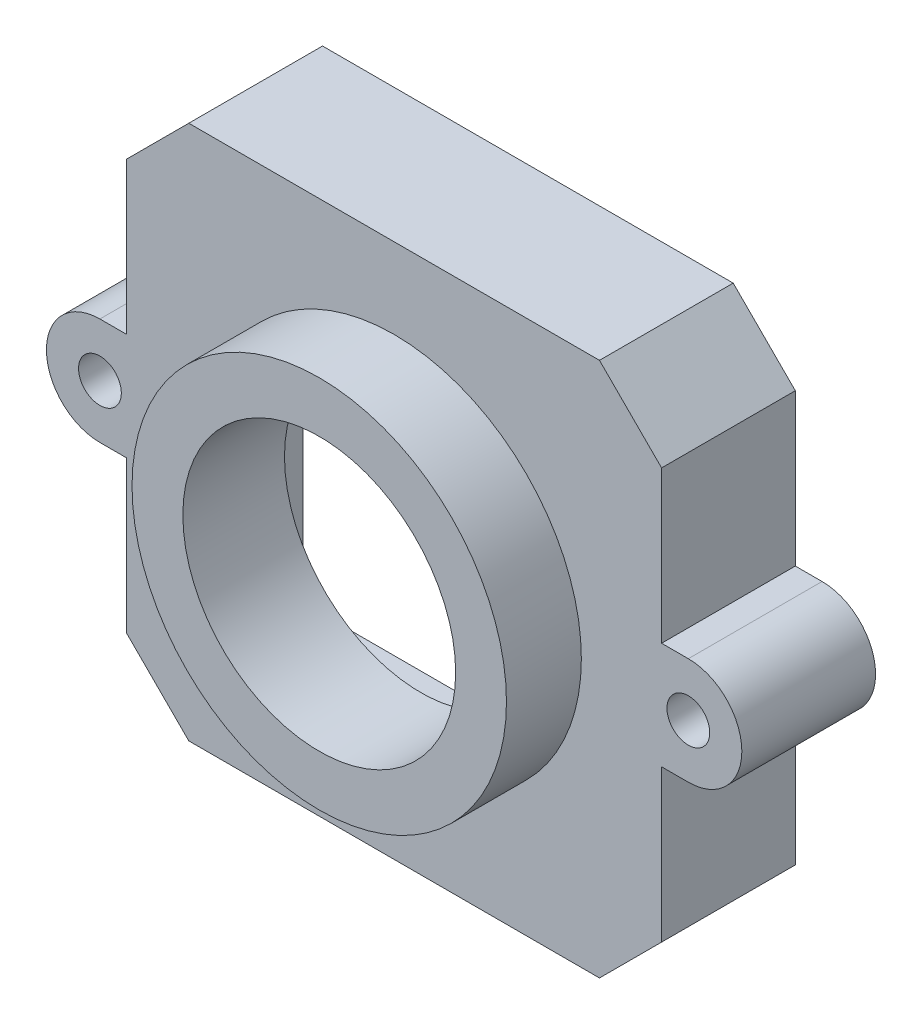
SolidWorks part; units mm, degrees
ref_plane "Front" through (0, 0, 0) normal (0, 0, 1) x (1, 0, 0)
ref_plane "Top" through (0, 0, 0) normal (0, 1, 0) x (1, 0, 0)
ref_plane "Right" through (0, 0, 0) normal (1, 0, 0) x (0, 0, -1)
sketch "Sketch1" plane through (0, 0, 0) normal (0, 0, 1) x (1, 0, 0)
  line L0 (-10, 7.6777) -> (-7.6777, 10)
  line L1 (-10, 10) -> (10, 10)
  line L2 (-10, 10) -> (-10, -10)
  line L3 (-10, -10) -> (10, -10)
  line L4 (10, 10) -> (10, -10)
  line L5 (7.6777, 10) -> (10, 7.6777)
  line L6 (-10, -7.6777) -> (-7.6777, -10)
  line L7 (7.6777, -10) -> (10, -7.6777)
  line L8 (10, 2) -> (11, 2)
  line L9 (10, -2) -> (11, -2)
  line L10 (-10, 2) -> (-11, 2)
  line L11 (-10, -2) -> (-11, -2)
  line L12 (-8.4, 7.0149) -> (-8.4, -7.0149)
  line L13 (-8.4, -7.0149) -> (-7.0149, -8.4)
  line L14 (-7.0149, -8.4) -> (7.0149, -8.4)
  line L15 (7.0149, -8.4) -> (8.4, -7.0149)
  line L16 (8.4, -7.0149) -> (8.4, 7.0149)
  line L17 (8.4, 7.0149) -> (7.0149, 8.4)
  line L18 (7.0149, 8.4) -> (-7.0149, 8.4)
  line L19 (-7.0149, 8.4) -> (-8.4, 7.0149)
  arc A0 (11, 2) -> (11, -2) centre (11, 0) cw
  arc A1 (-11, -2) -> (-11, 2) centre (-11, 0) cw
  circle A2 centre (-11, 0) radius 0.8
  circle A3 centre (11, 0) radius 0.8
  point P4 (0, 10)
  point P5 (10, 0)
  dimension "D4" = 2
  dimension "D5" = 2
  dimension "D7" = 1.6
  dimension "D8" = 1.6
  dimension "D1" = 25
  dimension "D2" = 20
  dimension "D3" = 20
  dimension "D6" = 11
  dimension "D9" = 11
  dimension "D10" = 1.6
  dimension "D11" = 1.6
  dimension "D12" = 1.6
  dimension "D13" = 1.6
  dimension "D14" = 1.6
  dimension "D15" = 1.6
  dimension "D16" = 1.6
  dimension "D17" = 1.6
extrude "Roof" add sketch "Sketch1" along normal blind 1 contours L3 L7 L4 L5 L1 L0 L2 L6 L19 L18 L17 L16 L15 L14 L13 L12 | L18 L19 L12 L13 L14 L15 L16 L17 | A1 L11 L2 L10 A2 | A0 L8 L4 L9 A3 region at (-8.6388, 8.6388, 0) region at (-10.05, 0, 0) region at (10.5, 1.95, 0) region at (0, 0, 0)
extrude "Walls" add sketch "Sketch1<3>" against normal blind 4 contours L3 L7 L4 L5 L1 L0 L2 L6 L19 L18 L17 L16 L15 L14 L13 L12 | A0 L8 L4 L9 A3 | A1 L11 L2 L10 A2 region at (-8.6388, 8.6388, 0) region at (-10.05, 0, 0) region at (10.5, 1.95, 0)
sketch "Sketch1<3>" plane through (0, 0, 0) normal (0, 0, 1) x (1, 0, 0) same geometry as "Sketch1"
sketch "Sketch2" plane through (0, 0, 1) normal (0, 0, 1) x (1, 0, 0)
  circle A0 centre (0, 0) radius 5.1
  circle A1 centre (0, 0) radius 7
  dimension "D1" = 14
  dimension "D2" = 10.2
extrude "Screw hole in roof" cut sketch "Sketch2" against normal through all contours A0 region at (0, 0, 1)
extrude "Screw holder" add sketch "Sketch2<3>" along normal blind 2.8
sketch "Sketch2<3>" plane through (0, 0, 1) normal (0, 0, 1) x (1, 0, 0) same geometry as "Sketch2"
